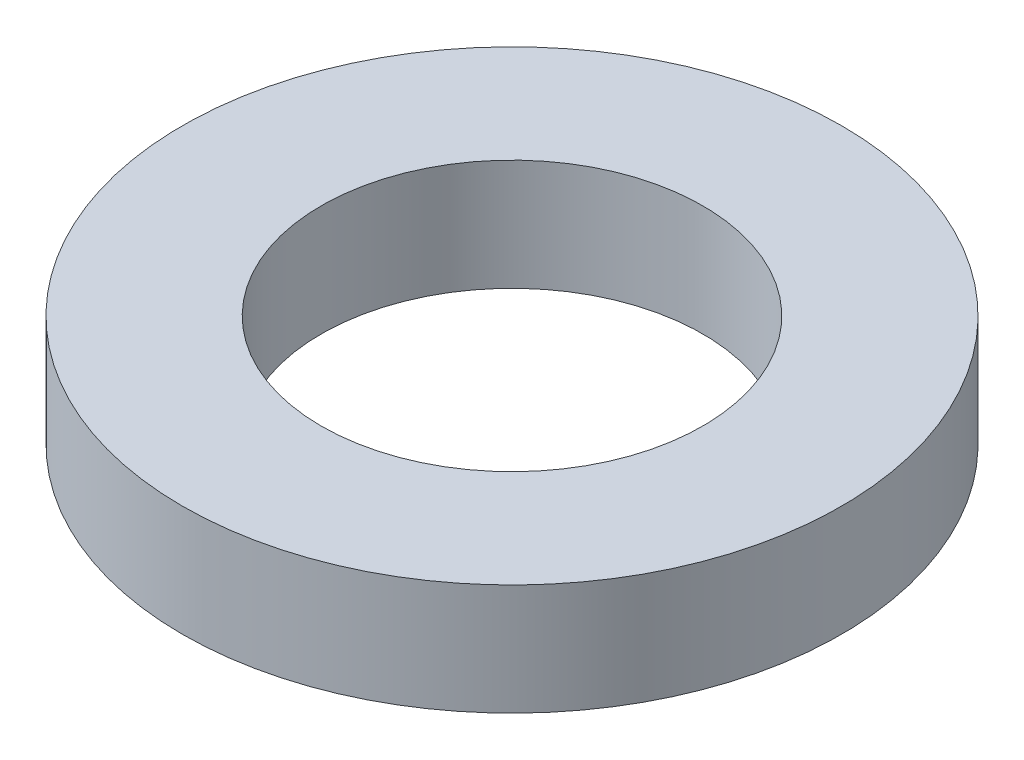
SolidWorks part; units mm, degrees
ref_plane "Front Plane" through (0, 0, 0) normal (0, 0, 1) x (1, 0, 0)
ref_plane "Top Plane" through (0, 0, 0) normal (0, 1, 0) x (1, 0, 0)
ref_plane "Right Plane" through (0, 0, 0) normal (1, 0, 0) x (0, 0, -1)
sketch "Sketch1" plane through (0, 0, 0) normal (0, 1, 0) x (1, 0, 0)
  circle A0 centre (0, 0) radius 47.5
  dimension "FLANGE_OD" = 95
extrude "Boss-Extrude1" add sketch "Sketch1" along normal blind 16
sketch "Sketch2" plane through (0, 0, 0) normal (0, 1, 0) x (1, 0, 0)
  circle A0 centre (0, 0) radius 27.5
  dimension "BORE_D" = 55
extrude "Cut-Extrude1" cut sketch "Sketch2" along normal through all
sketch "Sketch3" plane through (0, 16, 0) normal (0, 1, 0) x (1, 0, 0)
  circle A0 centre (0, 0) radius 16.2453 construction
  circle A1 centre (-16.2453, 0) radius 2.8849
  dimension "BOLT_D" = 5.7697
  dimension "BOLT_PCD" = 32.4906
extrude "Cut-Extrude2" cut sketch "Sketch3" against normal blind 15.3947 rebuild error yes
pattern_circular "CirPattern1" count 6 over 360 rebuild error yes
